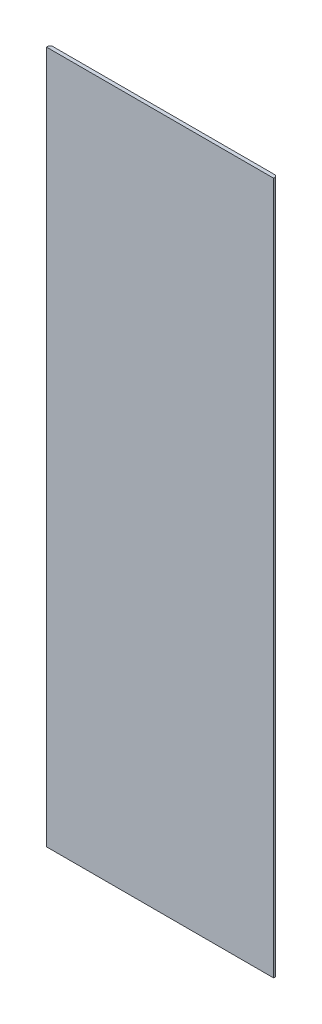
SolidWorks part; units mm, degrees
material "6061-T6 (SS)"
ref_plane "Front Plane" through (0, 0, 0) normal (0, 0, 1) x (1, 0, 0)
ref_plane "Top Plane" through (0, 0, 0) normal (0, 1, 0) x (1, 0, 0)
ref_plane "Right Plane" through (0, 0, 0) normal (1, 0, 0) x (0, 0, -1)
sketch "Sketch1" plane through (0, 0, 0) normal (0, 0, 1) x (1, 0, 0)
  line L1 (49.2063, -150) -> (-49.2062, -150)
  line L2 (49.2063, -150) -> (49.2063, 150)
  line L3 (49.2063, 150) -> (-49.2062, 150)
  line L4 (-49.2062, -150) -> (-49.2062, 150)
  line L5 (49.2063, -150) -> (-49.2062, 150) construction
  line L6 (49.2063, 150) -> (-49.2062, -150) construction
  point P0 (0, 0)
  dimension "D1" = 300
  dimension "D2" = 98.4125
extrude "Boss-Extrude1" add sketch "Sketch1" along normal mid plane 1.5875
chamfer "Chamfer1" distance 0.7937 angle 45 2 edges at (-49.2062, 0, -0.7937) (49.2063, 0, -0.7937)
